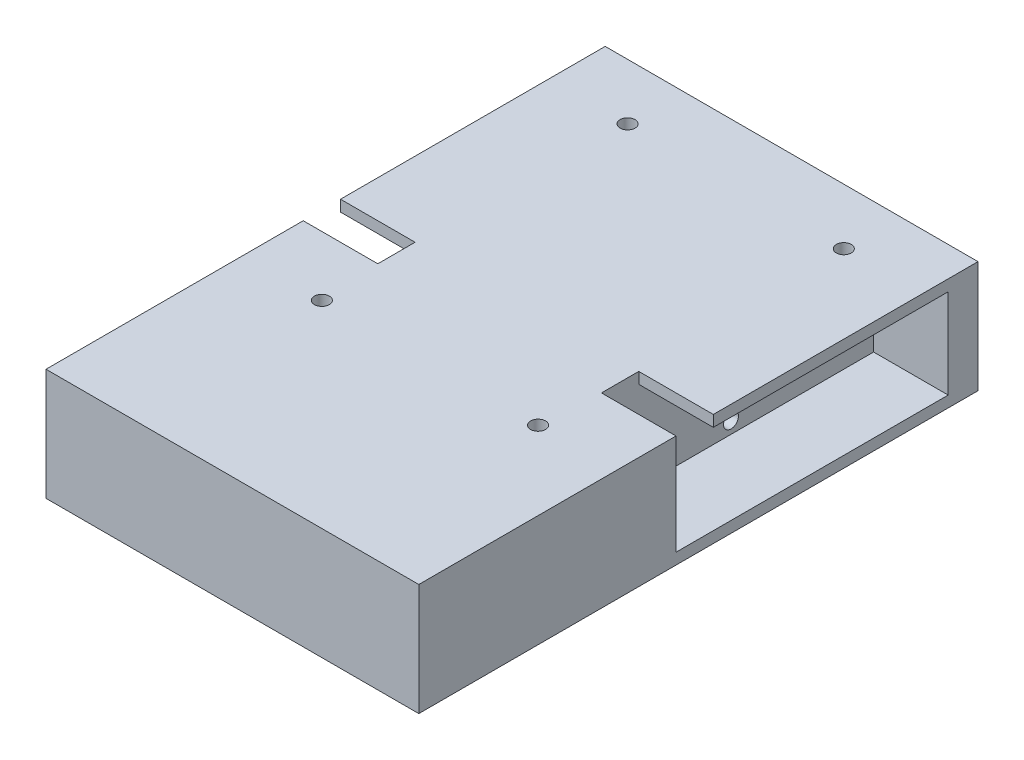
SolidWorks part; units mm, degrees
ref_plane "Front Plane" through (0, 0, 0) normal (0, 0, 1) x (1, 0, 0)
ref_plane "Top Plane" through (0, 0, 0) normal (0, 1, 0) x (1, 0, 0)
ref_plane "Right Plane" through (0, 0, 0) normal (1, 0, 0) x (0, 0, -1)
sketch "Sketch1" plane through (0, 0, 0) normal (0, 1, 0) x (1, 0, 0)
  line L1 (-50, 75) -> (50, 75)
  line L2 (-50, 75) -> (-50, -75)
  line L3 (-50, -75) -> (50, -75)
  line L4 (50, 75) -> (50, -75)
  line L5 (-50, 75) -> (50, -75) construction
  line L6 (-50, -75) -> (50, 75) construction
  point P0 (0, 0)
  dimension "D1" = 100
  dimension "D2" = 150
extrude "box" add sketch "Sketch1" against normal blind 30
sketch "Sketch2" plane through (50, 0, 0) normal (1, 0, 0) x (0, 0, -1)
  line L0 (0, 0) -> (0, -30) construction
  line L1 (-75, -30) -> (75, -30) construction
  line L2 (-75, -15) -> (75, -15) construction
  line L3 (-75, -30) -> (-75, 0) construction
  line L4 (75, -30) -> (75, 0) construction
  line L6 (-6, -3) -> (67, -3)
  line L7 (-6, -3) -> (-6, -27)
  line L8 (-6, -27) -> (67, -27)
  line L9 (67, -3) -> (67, -27)
  line L10 (-6, -3) -> (67, -27) construction
  line L11 (-6, -27) -> (67, -3) construction
  point P11 (30.5, -15)
  dimension "D1" = 24
  dimension "D2" = 73
  dimension "D3" = 8
extrude "motor compartment" cut sketch "Sketch2" against normal blind 20
sketch "Sketch3" plane through (50, 0, 0) normal (1, 0, 0) x (0, 0, -1)
  line L0 (-75, 0) -> (75, 0) construction
  line L1 (-6, -3) -> (4, -3)
  line L2 (-6, -3) -> (-6, 0)
  line L3 (-6, 0) -> (4, 0)
  line L4 (4, -3) -> (4, 0)
  dimension "D1" = 10
extrude "motor wire passthrough" cut sketch "Sketch3" against normal up to surface (20 mm away) up to face at (30, -15, -30.5)
sketch "Sketch4" plane through (30, 0, 0) normal (1, 0, 0) x (0, 0, -1)
  line L0 (67, -15) -> (-49933, -15) construction
  line L1 (67, -27) -> (67, -3) construction
  line L2 (67, -27) -> (67, -3) construction
  line L3 (67, -27) -> (67, -3) construction
  line L4 (28.75, -3) -> (28.75, -27) construction
  line L5 (67, -3) -> (4, -3) construction
  line L6 (-6, -27) -> (67, -27) construction
  circle A0 centre (63, -15) radius 1.75
  circle A1 centre (28.75, -6.25) radius 2
  circle A2 centre (28.75, -23.75) radius 2
  point P4 (67, -15)
  dimension "D1" = 3.5
  dimension "D4" = 4
  dimension "D2" = 4
  dimension "D3" = 34.25
  dimension "D5" = 8.75
extrude "motor screw mount" cut sketch "Sketch4" against normal blind 10
mirror "motor compartment mirror" about plane through (0, 0, 0) normal (1, 0, 0) of "motor screw mount", "motor compartment", "motor wire passthrough"
sketch "Sketch5" plane through (0, 0, 0) normal (0, 1, 0) x (1, 0, 0)
  line L0 (0, 75) -> (0, -75) construction
  line L1 (50, 75) -> (-50, 75) construction
  line L2 (-50, -75) -> (50, -75) construction
  line L3 (50, 60) -> (-50, 60) construction
  line L4 (50, 4) -> (50, 75) construction
  line L5 (-50, 75) -> (-50, 4) construction
  line L6 (50, -22) -> (-50, -22) construction
  line L7 (50, -75) -> (50, -6) construction
  line L8 (-50, -6) -> (-50, -75) construction
  circle A0 centre (-29, 60) radius 2
  circle A1 centre (-29, -22) radius 2
  circle A2 centre (29, 60) radius 2
  circle A3 centre (29, -22) radius 2
  dimension "D4" = 4
  dimension "D3" = 4
  dimension "D1" = 15
  dimension "D2" = 82
  dimension "D5" = 29
extrude "Maker Pi mount holes" cut sketch "Sketch5" against normal blind 8
sketch "Sketch6" plane through (0, -30, 0) normal (0, -1, 0) x (1, 0, 0)
  line L0 (0, 0) -> (0, 75) construction
  line L1 (-50, 75) -> (50, 75) construction
  line L2 (-50, 75) -> (50, 75) construction
  line L4 (-12, 65) -> (12, 65)
  line L5 (-12, 65) -> (-12, 37)
  line L6 (-12, 37) -> (12, 37)
  line L7 (12, 65) -> (12, 37)
  line L8 (-12, 65) -> (12, 37) construction
  line L9 (-12, 37) -> (12, 65) construction
  point P5 (0, 51)
  dimension "D1" = 24
  dimension "D2" = 28
  dimension "D3" = 10
extrude "caster mount" cut sketch "Sketch6" against normal blind 1
equation "\"D5@Sketch4\"=17.5mm/2"
equation "\"D4@Sketch5\"=\"D3@Sketch5\""
equation "\"D5@Sketch5\"=58mm/2"
